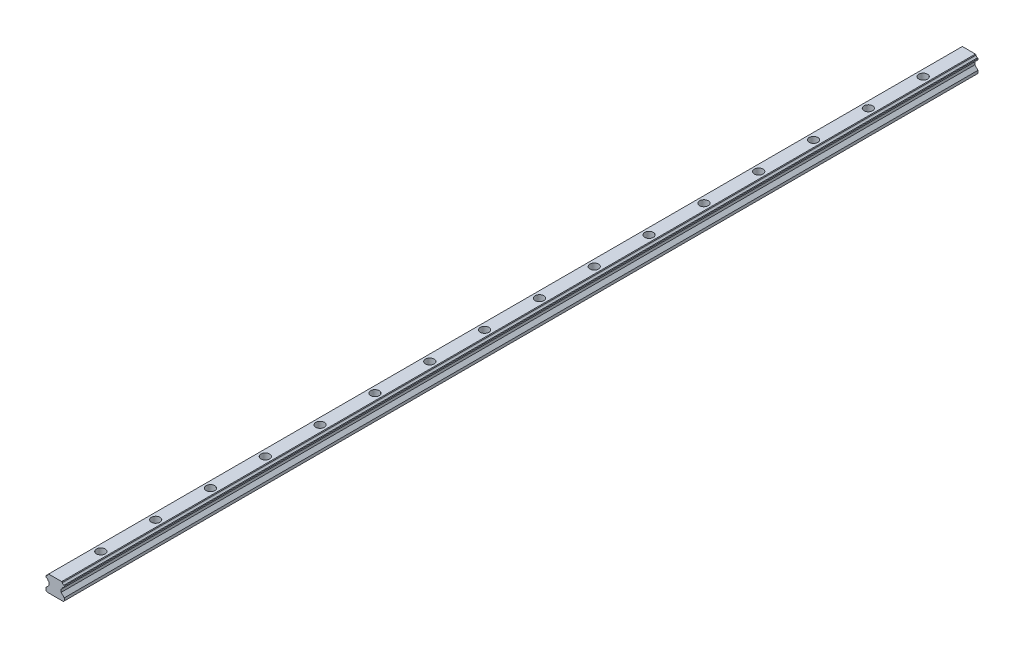
SolidWorks part; units mm, degrees
material "Plain Carbon Steel"
ref_plane "Front Plane" through (0, 0, 0) normal (0, 0, 1) x (1, 0, 0)
ref_plane "Top Plane" through (0, 0, 0) normal (0, 1, 0) x (1, 0, 0)
ref_plane "Right Plane" through (0, 0, 0) normal (1, 0, 0) x (0, 0, -1)
sketch "Sketch1" plane through (0, 0, 0) normal (0, 0, 1) x (1, 0, 0)
  line L0 (0, 13.3681) -> (0, -3.2505) construction
  line L1 (-6.55, -4.115) -> (-6.55, -7.045)
  line L2 (-6.55, -5.58) -> (0, -5.58) construction
  line L3 (-6.55, -7.045) -> (-10, -10.495)
  line L4 (-10, -10.495) -> (-10, -13.495)
  line L5 (-10, -13.495) -> (-9, -14.495)
  line L6 (-9, -14.495) -> (0, -14.495)
  line L7 (-6.55, -4.115) -> (-7.7681, -2.8969)
  line L8 (-10, -0.665) -> (-10, 0.665)
  line L9 (-10, 0.665) -> (-9.4697, 1.1953)
  line L10 (-7.16, 3.505) -> (0, 3.505)
  line L11 (-10, -0.665) -> (-10, -10.495) construction
  line L12 (-10, 0) -> (0, 0) construction
  line L13 (-7.7681, 2.8969) -> (-7.16, 3.505)
  line L14 (-9.4697, -1.1953) -> (-10, -0.665)
  line L15 (0, 3.505) -> (0, -14.495)
  arc A0 (-9.4697, 1.1953) -> (-7.7681, 2.8969) centre (-9.7486, 3.1758) ccw
  arc A1 (-9.4697, -1.1953) -> (-7.7681, -2.8969) centre (-9.7486, -3.1758) cw
  dimension "D10" = 4
  dimension "D1" = 2.93
  dimension "D2" = 6.55
  dimension "D3" = 9
  dimension "D4" = 7.16
  dimension "D5" = 3
  dimension "D6" = 1.33
  dimension "D7" = 18
  dimension "D8" = 45
  dimension "D9" = 45
  dimension "D11" = 0.75
  dimension "D12" = 0.86
extrude "Boss-Extrude1" add sketch "Sketch1" along normal blind 500
mirror "Mirror1" about plane through (0, 3.505, 500) normal (-1, 0, 0) of "Boss-Extrude1"
sketch "Sketch2" plane through (0, 3.505, 0) normal (0, 1, 0) x (1, 0, 0)
  line L0 (0, 130.187) -> (0, 31.9327) construction
  line L1 (7.16, 0) -> (-7.16, 0) construction
  circle A0 centre (0, -30) radius 3
  dimension "D1" = 6
  dimension "D2" = 30
extrude "Cut-Extrude1" cut sketch "Sketch2" against normal through all
sketch "Sketch3" plane through (0, 3.505, 0) normal (0, 1, 0) x (1, 0, 0)
  circle A0 centre (0, -30) radius 4.75
  dimension "D1" = 9.5
extrude "Cut-Extrude2" cut sketch "Sketch3" against normal blind 8.5
pattern_linear "LPattern1" count 100 spacing 60 along (0, 0, 1) of "Cut-Extrude1", "Cut-Extrude2"
mirror "Mirror2" about plane through (-9.7486, -3.1758, 0) normal (0, 0, -1) of bodies 106
equation "\"length\"= 1000mm"
equation "\"D1@Boss-Extrude1\" = ( \"work_area_width\" - 100 ) / 2"
equation "\"M5_tap\"=4.2mm\t\t\t\t\t\t\t' Below you can do mesurements as follows: cm, mm, ft, in, m, "
equation "\"M5_clearence\"=5.5mm"
equation "\"M6_tap\"=5mm"
equation "\"M6_clearence\"=6.6mm"
equation "\"work_area_width\"=1100mm"
equation "\"work_area_depth\"=900mm"
